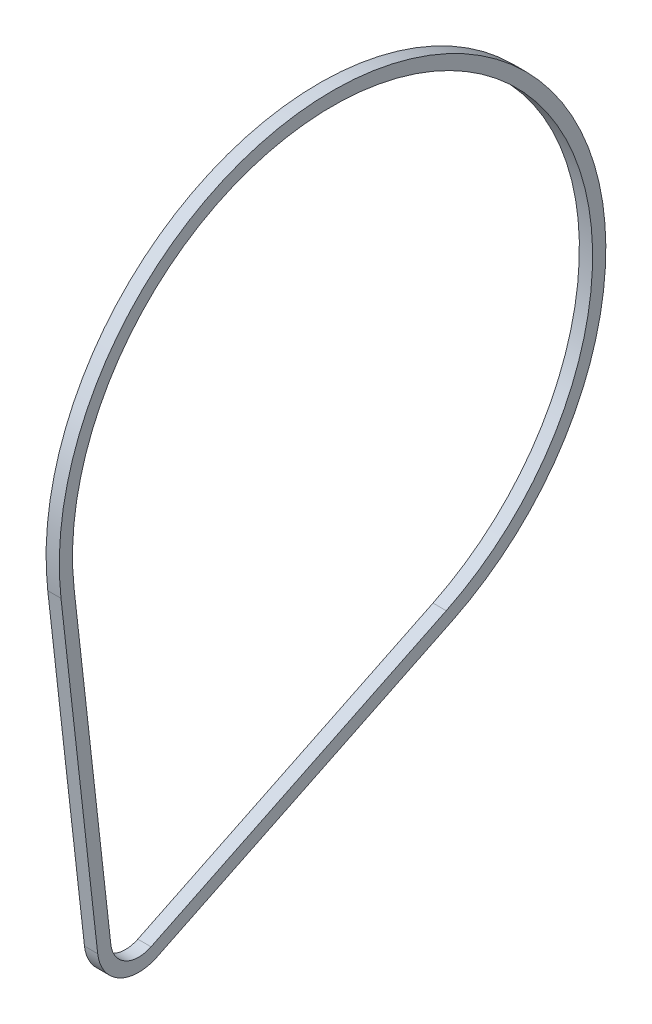
SolidWorks part; units mm, degrees
material "Plain Carbon Steel"
ref_plane "Front Plane" through (0, 0, 0) normal (0, 0, 1) x (1, 0, 0)
ref_plane "Top Plane" through (0, 0, 0) normal (0, 1, 0) x (1, 0, 0)
ref_plane "Right Plane" through (0, 0, 0) normal (1, 0, 0) x (0, 0, -1)
sketch "Sketch1" plane through (0, 0, 0) normal (1, 0, 0) x (0, 0, -1)
  line L0 (117.6178, 128.0353) -> (131.7183, 2.7221)
  line L1 (154.4324, -9.7812) -> (267.8531, 45.3369)
  line L2 (122.6659, 128.6034) -> (136.7664, 3.2901)
  line L3 (152.212, -5.2121) -> (265.6327, 49.9059)
  arc A0 (136.7664, 3.2901) -> (152.212, -5.2121) centre (147.4937, 4.4971) ccw
  arc A1 (131.7183, 2.7221) -> (154.4324, -9.7812) centre (147.4937, 4.4971) ccw
  arc A2 (265.6327, 49.9059) -> (122.6659, 128.6034) centre (221.9593, 139.7761) ccw
  arc A3 (267.8531, 45.3369) -> (117.6178, 128.0353) centre (221.9593, 139.7761) ccw
  arc A4 (268.7158, 45.761) -> (271.5256, 47.2116) centre (221.9593, 139.7761) ccw construction
  arc A6 (159.6544, 2.8248) -> (158.5539, -0.8276) centre (159.7753, 0.7963) ccw construction
  dimension "D1" = 5.08
  dimension "D2" = 5.08
extrude "Boss-Extrude1" add sketch "Sketch1" along normal blind 5.08
